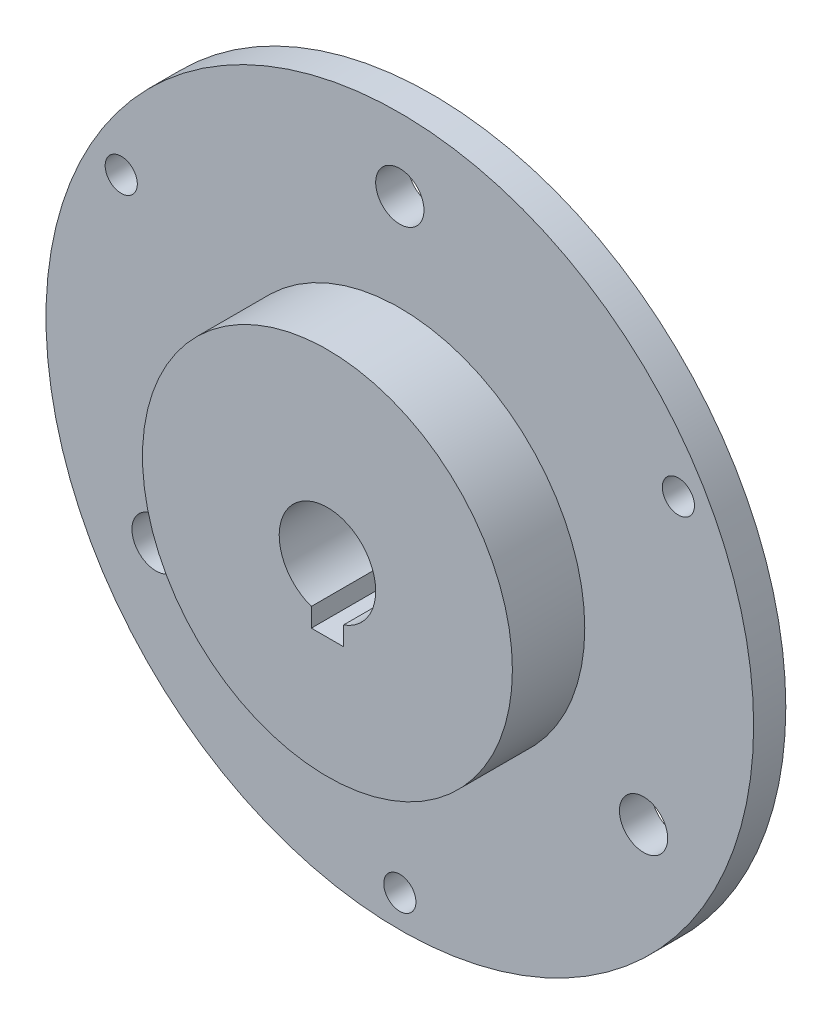
SolidWorks part; units mm, degrees
material "201 Stal nierdzewna odprężona (SS)"
ref_plane "Płaszczyzna przednia" through (0, 0, 0) normal (0, 0, 1) x (1, 0, 0)
ref_plane "Płaszczyzna górna" through (0, 0, 0) normal (0, 1, 0) x (1, 0, 0)
ref_plane "Płaszczyzna prawa" through (0, 0, 0) normal (1, 0, 0) x (0, 0, -1)
sketch "Szkic1" plane through (0, 0, 0) normal (1, 0, 0) x (0, 0, -1)
  line L0 (0, 0) -> (20.2052, 0) construction
  line L73 (29, 6) -> (0, 6)
  line L74 (9, 23) -> (0, 23)
  line L75 (29, 6) -> (29, 13)
  line L76 (13, 15) -> (27, 15)
  line L77 (0, 6) -> (0, 23)
  line L78 (9, 23) -> (9, 44)
  line L79 (9, 44) -> (13, 44)
  line L80 (13, 44) -> (13, 15)
  line L81 (27, 15) -> (29, 13)
revolve "Obrót1" add sketch "Szkic1" angle 360 about L0
sketch "Szkic2" plane through (0, 0, 0) normal (0, 0, 1) x (1, 0, 0)
  line L1 (-2, -4.801) -> (2, -4.801)
  line L2 (-2, -4.801) -> (-2, -8)
  line L3 (-2, -8) -> (2, -8)
  line L4 (2, -4.801) -> (2, -8)
  dimension "D1" = 8
  dimension "D2" = 2
  dimension "D3" = 2
extrude "Wytnij-wyciągnięcie1" cut sketch "Szkic2" against normal through all
sketch "Szkic3" plane through (0, 0, -9) normal (0, 0, 1) x (1, 0, 0)
  circle A0 centre (0, -40) radius 2
  circle A1 centre (0, 35) radius 3
  circle A2 centre (30.3109, -17.5) radius 3
  circle A3 centre (-34.641, 20) radius 2
  circle A4 centre (-30.3109, -17.5) radius 3
  circle A5 centre (34.641, 20) radius 2
  point P15 (0, 0)
  dimension "D1" = 4
  dimension "D3" = 6
  dimension "D2" = 40
  dimension "D4" = 35
  dimension "D5" = 3
extrude "Wytnij-wyciągnięcie2" cut sketch "Szkic3" against normal through all
